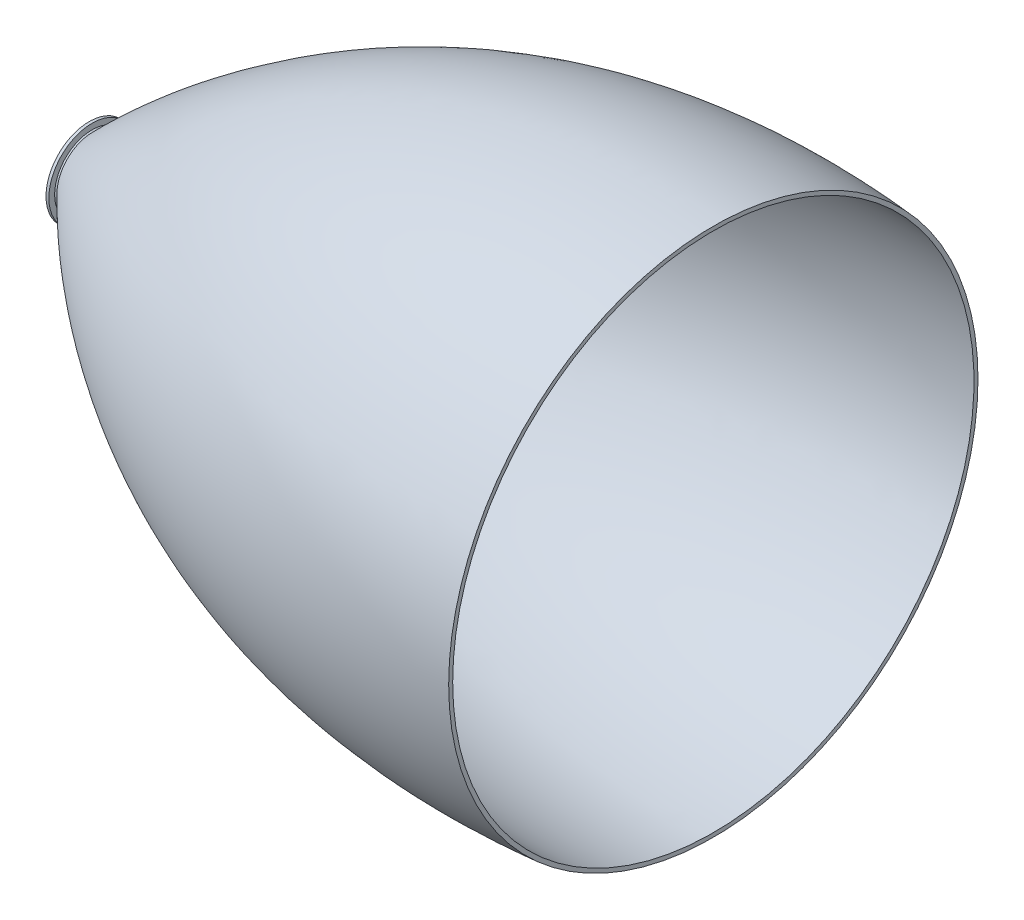
SolidWorks part; units mm, degrees
material "A286 Iron Base Superalloy"
ref_plane "Front Plane" through (0, 0, 0) normal (0, 0, 1) x (1, 0, 0)
ref_plane "Top Plane" through (0, 0, 0) normal (0, 1, 0) x (1, 0, 0)
ref_plane "Right Plane" through (0, 0, 0) normal (1, 0, 0) x (0, 0, -1)
sketch "Sketch1" plane through (0, 0, 0) normal (0, 0, 1) x (1, 0, 0)
  line L0 (-1229.8282, 0) -> (1426.3964, 0) construction
  line L1 (0, -70.104) -> (0, 70.104) construction
  line L2 (0, 0) -> (1371.6, 0) construction
  line L3 (1371.6, -576) -> (1371.6, 576) construction
  line L5 (1371.6, 584.89) -> (1371.6, 576)
  line L6 (0, -78.994) -> (0, -70.104)
  line L7 (1371.6, -584.89) -> (1371.6, -576)
  line L8 (-412.8242, -144.8099) -> (-412.8242, 144.8099) construction
  line L9 (-412.8242, 144.8099) -> (-412.8242, 153.6999)
  line L10 (-412.8242, -144.8099) -> (-412.8242, -153.6999)
  spline S0 degree 2 poles (0, 70.104) (587.1414, 578.5372) (1371.6, 576) knots 0 0 0 1 1 1
  spline S1 degree 2 poles (0, -70.104) (587.1414, -578.5372) (1371.6, -576) knots 0 0 0 1 1 1
  spline S2 degree 2 poles (0, -78.994) (562.2239, -652.3767) (1371.6, -584.89) knots 0 0 0 1 1 1
  spline S3 degree 2 poles (0, -70.104) (587.1414, -578.5372) (1371.6, -576) knots 0 0 0 1 1 1
  spline S4 degree 2 poles (0, 78.994) (562.2239, 652.3767) (1371.6, 584.89) knots 0 0 0 1 1 1
  spline S5 degree 2 poles (0, 70.104) (-195.4497, 157.4108) (-412.8242, 144.8099) knots 0 0 0 1 1 1
  spline S6 degree 2 poles (0, -70.104) (-195.4497, -157.4108) (-412.8242, -144.8099) knots 0 0 0 1 1 1
  spline S7 degree 2 poles (0, -78.994) (-192.7304, -176.7061) (-412.8242, -153.6999) knots 0 0 0 1 1 1
  spline S9 degree 2 poles (0, 78.994) (-192.7304, 176.7061) (-412.8242, 153.6999) knots 0 0 0 1 1 1
  point P8 (0, 0)
  point P14 (1371.6, 0)
  point P22 (-412.8242, 0)
  point P23 (581.284, 429.4836)
  point P27 (581.284, 475.6813)
  dimension "D4" = 8.89
  dimension "D1" = 140.208
  dimension "D2" = 1371.6
  dimension "D3" = 1152
  dimension "D5" = 8.89
  dimension "D6" = 8.89
  dimension "D7" = 289.6197
revolve "Revolve3" add sketch "Sketch1" angle 360 about L0 region at (1353.0082, 580.445, 0)
ref_plane "Plane1" through (0, 0, 0) normal (1, 0, 0) x (0, 0, -1)
ref_plane "Plane2" through (-7.62, 0, 0) normal (-1, 0, 0) x (0, 0, 1)
sketch "Sketch4" plane through (-7.62, 0, 0) normal (-1, 0, 0) x (0, 0, 1)
  line L1 (-1213.2286, 638.9142) -> (1085.9115, 638.9142)
  line L2 (-1213.2286, 638.9142) -> (-1213.2286, -445.9528)
  line L3 (-1213.2286, -445.9528) -> (1085.9115, -445.9528)
  line L4 (1085.9115, 638.9142) -> (1085.9115, -445.9528)
extrude "Cut-Extrude1" cut sketch "Sketch4" along normal blind 554.228
sketch "Sketch5" plane through (-7.62, 0, 0) normal (-1, 0, 0) x (0, 0, 1)
  circle A0 centre (0, 0) radius 95.5048
  circle A1 centre (0, 0) radius 82.8048 construction
  circle A2 centre (0, 0) radius 82.8048
  dimension "D1" = 12.7
extrude "Boss-Extrude1" add sketch "Sketch5" against normal blind 6.35 separate body
